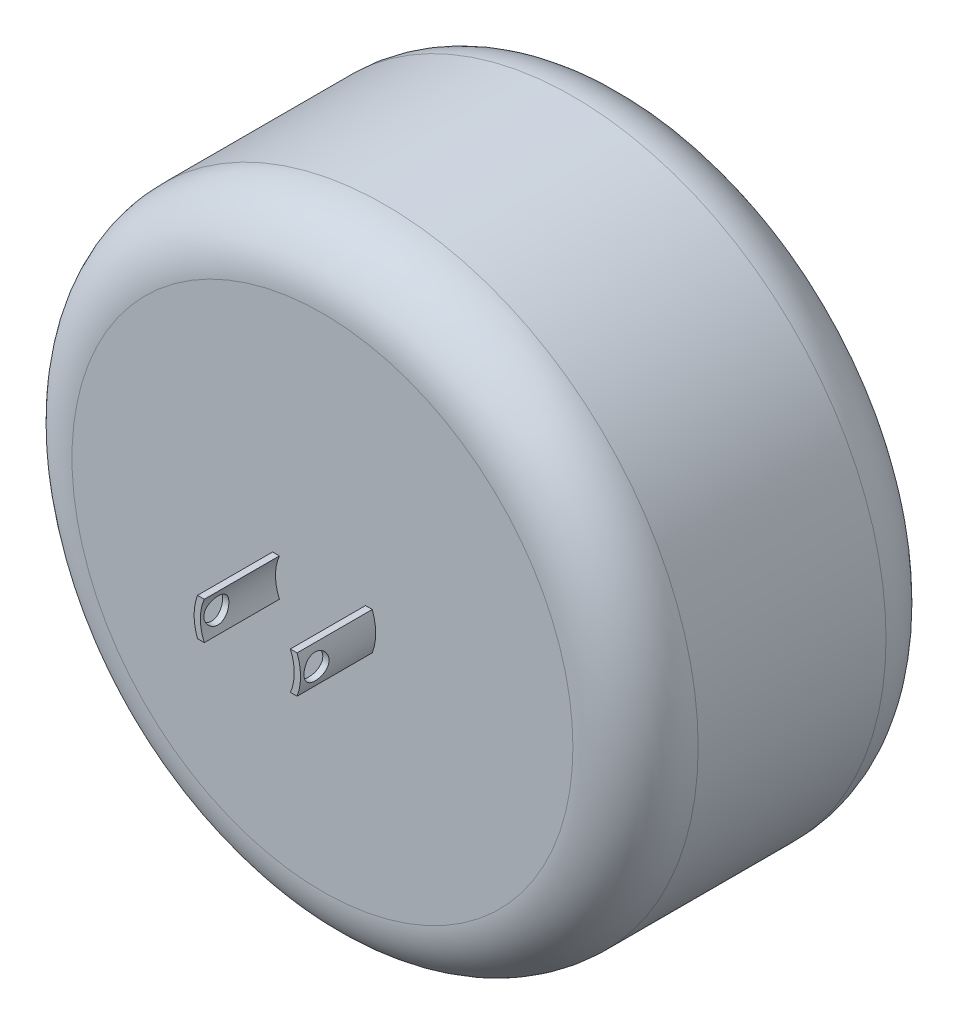
SolidWorks part; units mm, degrees
ref_plane "Front Plane" through (0, 0, 0) normal (0, 0, 1) x (1, 0, 0)
ref_plane "Top Plane" through (0, 0, 0) normal (0, 1, 0) x (1, 0, 0)
ref_plane "Right Plane" through (0, 0, 0) normal (1, 0, 0) x (0, 0, -1)
sketch "Sketch2" plane through (0, 0, 0) normal (0, 0, 1) x (1, 0, 0)
  circle A0 centre (0, 0) radius 50
extrude "Boss-Extrude1" add sketch "Sketch2" along normal blind 50
sketch "Sketch3" plane through (0, 0, 0) normal (0, 0, -1) x (-1, 0, 0)
  circle A0 centre (0, 0) radius 13
extrude "Boss-Extrude2" add sketch "Sketch3" along normal blind 12
sketch "Sketch7" plane through (0, 0, -12) normal (0, 0, -1) x (-1, 0, 0)
  circle A0 centre (0, 0) radius 12
extrude "Cut-Extrude3" cut sketch "Sketch7" against normal blind 12
sketch "Sketch11" plane through (0, 0, 50) normal (0, 0, 1) x (1, 0, 0)
  circle A0 centre (0, 0) radius 8.5
extrude "Boss-Extrude3" add sketch "Sketch11" along normal blind 12
sketch "Sketch12" plane through (0, 0, 62) normal (0, 0, 1) x (1, 0, 0)
  circle A0 centre (0, 0) radius 7.5
extrude "Cut-Extrude7" cut sketch "Sketch12" against normal blind 12
sketch "Sketch13" plane through (0, 0, 0) normal (1, 0, 0) x (0, 0, -1)
  line L0 (-56, 8.5) -> (-56, -8.5407) construction
  line L3 (-56.6416, 0) -> (-62.2472, 0) construction
  line L4 (-50, 8.5) -> (-62, 8.5) construction
  line L5 (-62.2472, 0) -> (-50.2472, 0) construction
sketch "Sketch15" plane through (0, 0, 0) normal (1, 0, 0) x (0, 0, -1)
  line L0 (-50, 0) -> (-59.4444, 0) construction
  line L1 (-50, 8.5) -> (-50, -8.5) construction
  line L2 (-56.6416, 0) -> (-62.2472, 0) construction
  circle A0 centre (-59.4444, 0) radius 2
extrude "Cut-Extrude8" cut sketch "Sketch15" against normal blind 12 and the other way blind 12
sketch "Sketch16" plane through (0, 0, 0) normal (1, 0, 0) x (0, 0, -1)
  line L0 (-62, 0) -> (-50, 0) construction
  line L1 (-62, 8.5) -> (-62, -8.5) construction
  line L2 (-50, 8.5) -> (-50, -8.5) construction
  line L3 (-50, 0) -> (-50, 3) construction
  line L4 (-50, 50) -> (-50, -50) construction
  line L5 (-50, 3) -> (-62, 3)
  line L6 (-62, 3) -> (-62, 8.5)
  line L7 (-62, 8.5) -> (-50, 8.5)
  line L8 (-50, 8.5) -> (-50, 3)
  line L9 (-62, -8.5) -> (-50, -8.5)
  line L10 (-62, -3) -> (-62, -8.5)
  line L11 (-50, -3) -> (-62, -3)
  line L12 (-50, -8.5) -> (-50, -3)
extrude "Cut-Extrude9" cut sketch "Sketch16" against normal blind 12 and the other way blind 12
sketch "Sketch19" plane through (0, 0, 0) normal (0, 1, 0) x (1, 0, 0)
  line L0 (0, 0) -> (0, 7.94) construction
  circle A0 centre (0, 7.94) radius 2
extrude "Cut-Extrude12" cut sketch "Sketch19" against normal blind 16 and the other way blind 16
sketch "Sketch20" plane through (0, 0, 0) normal (0, 1, 0) x (1, 0, 0)
  line L1 (12, 12) -> (-12, 12) construction
  line L2 (0, 0) -> (-3, 0) construction
  line L3 (50, 0) -> (-50, 0) construction
  line L4 (-3, 0) -> (-3, 12)
  line L5 (-3, 12) -> (-13, 12)
  line L6 (-13, 12) -> (-13, 0)
  line L7 (-13, 0) -> (-3, 0)
  line L8 (3, 0) -> (3, 12)
  line L9 (3, 12) -> (13, 12)
  line L10 (13, 12) -> (13, 0)
  line L11 (13, 0) -> (3, 0)
extrude "Cut-Extrude13" cut sketch "Sketch20" against normal blind 16 and the other way blind 16
fillet "Fillet1" radius 10 2 edges at (50, 0, 0) (50, 0, 50)
